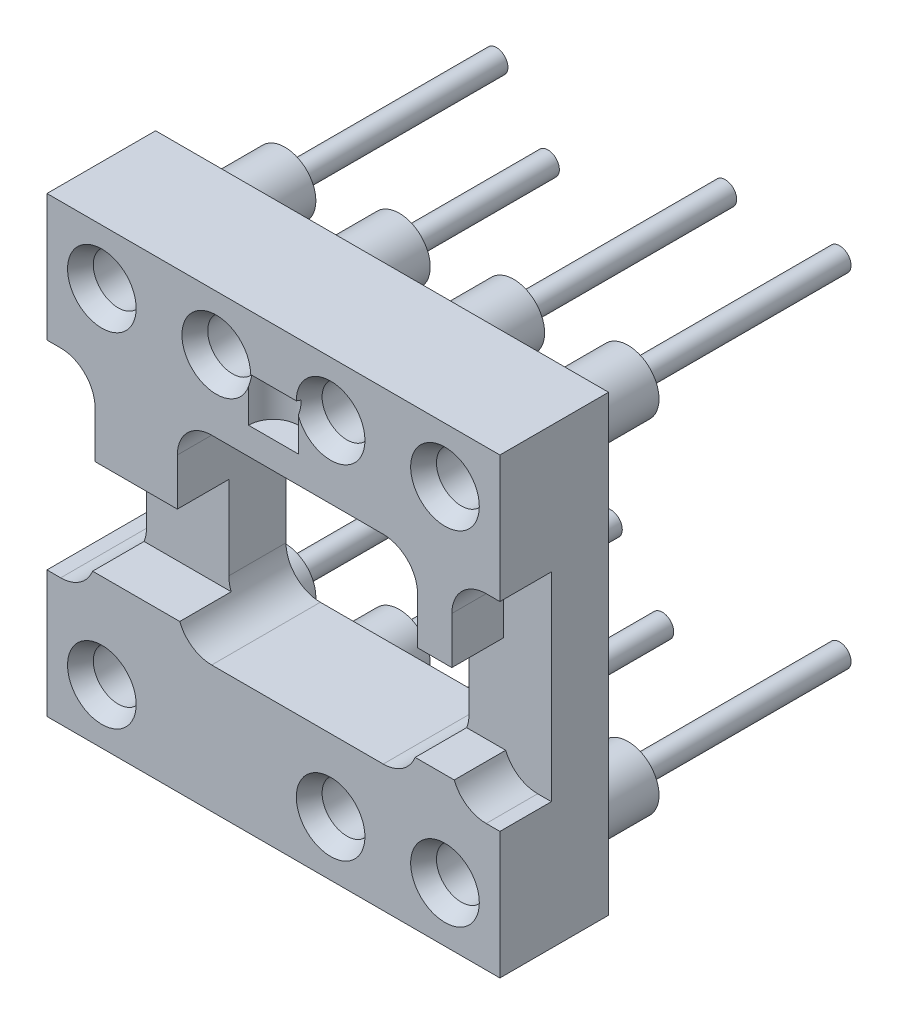
SolidWorks part; units mm, degrees
ref_plane "Plan de face" through (0, 0, 0) normal (0, 0, 1) x (1, 0, 0)
ref_plane "Plan de dessus" through (0, 0, 0) normal (0, 1, 0) x (1, 0, 0)
ref_plane "Plan de droite" through (0, 0, 0) normal (1, 0, 0) x (0, 0, -1)
sketch "Esquisse1" plane through (0, 0, 0) normal (0, 0, 1) x (1, 0, 0)
  line L0 (-5.0292, -5.0292) -> (5.0292, -5.0292)
  line L1 (5.0292, -5.0292) -> (5.0292, 5.0292)
  line L2 (5.0292, 5.0292) -> (-5.0292, 5.0292)
  line L3 (-5.0292, 5.0292) -> (-5.0292, -5.0292)
extrude "Boss.-Extru.1" add sketch "Esquisse1" against normal blind 2.413
sketch "Esquisse2" plane through (0, 0, -2.413) normal (0, 0, -1) x (-1, 0, 0)
  line L0 (2.1336, 2.2098) -> (-3.2004, 2.2098)
  line L1 (-3.2004, 2.2098) -> (-3.2004, -2.2098)
  line L2 (-3.2004, -2.2098) -> (2.1336, -2.2098)
  line L3 (2.1336, -2.2098) -> (2.1336, 2.2098)
extrude "Enlèv. mat.-Extru.1" cut sketch "Esquisse2" against normal through all
sketch "Esquisse3" plane through (3.2004, 0, 0) normal (-1, 0, 0) x (0, 0, 1)
  line L0 (0, -1.7272) -> (0, 0.4064)
  line L1 (0, 0.4064) -> (-1.143, 0.4064)
  line L2 (-1.143, 0.4064) -> (-1.143, -1.7272)
  line L3 (-1.143, -1.7272) -> (0, -1.7272)
extrude "Enlèv. mat.-Extru.2" cut sketch "Esquisse3" against normal through all
sketch "Esquisse4" plane through (0, 0, 0) normal (0, 0, 1) x (1, 0, 0)
  line L0 (5.0292, 2.2098) -> (3.9624, 2.2098)
  line L1 (3.9624, 2.2098) -> (3.9624, 0.4064)
  line L2 (3.9624, 0.4064) -> (5.0292, 0.4064)
  line L3 (5.0292, 0.4064) -> (5.0292, 2.2098)
extrude "Enlèv. mat.-Extru.3" cut sketch "Esquisse4" against normal blind 1.143
sketch "Esquisse5" plane through (0, 0, 0) normal (0, 0, 1) x (1, 0, 0)
  line L0 (5.0292, -1.7272) -> (4.0155, -1.7272)
  line L1 (4.7244, -2.2098) -> (5.0292, -2.2098)
  line L2 (5.0292, -2.2098) -> (5.0292, -1.7272)
  arc A0 (4.0155, -1.7272) -> (4.7244, -2.2098) centre (4.7244, -1.4478) ccw
extrude "Enlèv. mat.-Extru.4" cut sketch "Esquisse5" against normal blind 1.143
sketch "Esquisse6" plane through (0, 0, -2.413) normal (0, 0, -1) x (-1, 0, 0)
  line L0 (5.0292, -2.2098) -> (5.0292, 2.2098)
  line L1 (5.0292, 2.2098) -> (3.9624, 2.2098)
  line L2 (3.9624, 2.2098) -> (3.9624, -2.2098)
  line L3 (3.9624, -2.2098) -> (5.0292, -2.2098)
extrude "Enlèv. mat.-Extru.5" cut sketch "Esquisse6" against normal through all
sketch "Esquisse7" plane through (-2.1336, 0, 0) normal (1, 0, 0) x (0, 0, -1)
  line L0 (0, 0.4064) -> (0, -1.7272)
  line L1 (0, -1.7272) -> (1.143, -1.7272)
  line L2 (1.143, -1.7272) -> (1.143, 0.4064)
  line L3 (1.143, 0.4064) -> (0, 0.4064)
extrude "Enlèv. mat.-Extru.6" cut sketch "Esquisse7" against normal through all
ref_plane "Plan1" through (0, -3.81, 0) normal (0, 1, 0) x (-1, 0, 0)
sketch "Esquisse8" plane through (0, -3.81, 0) normal (0, 1, 0) x (-1, 0, 0)
  line L0 (-4.064, -8.763) -> (-3.81, -8.763)
  line L1 (-3.81, -8.763) -> (-3.81, -2.413)
  line L2 (-3.81, -2.413) -> (-4.4983, -2.413)
  line L3 (-4.4983, -2.413) -> (-4.4983, -4.064)
  line L4 (-4.4983, -4.064) -> (-4.064, -4.318)
  line L5 (-4.064, -4.318) -> (-4.064, -8.763)
  line L6 (-3.81, -8.763) -> (-3.81, -2.413) construction
revolve "Révolution1" add sketch "Esquisse8" angle 360 about L6 reverse direction yes
sketch "Esquisse9" plane through (0, -3.81, 0) normal (0, 1, 0) x (-1, 0, 0)
  line L0 (-1.524, -7.366) -> (-1.27, -7.366)
  line L1 (-1.27, -7.366) -> (-1.27, -2.413)
  line L2 (-1.27, -2.413) -> (-1.9583, -2.413)
  line L3 (-1.9583, -2.413) -> (-1.9583, -4.064)
  line L4 (-1.9583, -4.064) -> (-1.524, -4.318)
  line L5 (-1.524, -4.318) -> (-1.524, -7.366)
  line L6 (-1.27, -7.366) -> (-1.27, -2.413) construction
revolve "Révolution2" add sketch "Esquisse9" angle 360 about L6 reverse direction yes
sketch "Esquisse10" plane through (0, -3.81, 0) normal (0, 1, 0) x (-1, 0, 0)
  line L0 (1.016, -8.763) -> (1.27, -8.763)
  line L1 (1.27, -8.763) -> (1.27, -2.413)
  line L2 (1.27, -2.413) -> (0.5817, -2.413)
  line L3 (0.5817, -2.413) -> (0.5817, -4.064)
  line L4 (0.5817, -4.064) -> (1.016, -4.318)
  line L5 (1.016, -4.318) -> (1.016, -8.763)
  line L6 (1.27, -8.763) -> (1.27, -2.413) construction
revolve "Révolution3" add sketch "Esquisse10" angle 360 about L6 reverse direction yes
sketch "Esquisse11" plane through (0, -3.81, 0) normal (0, 1, 0) x (-1, 0, 0)
  line L0 (3.556, -8.763) -> (3.81, -8.763)
  line L1 (3.81, -8.763) -> (3.81, -2.413)
  line L2 (3.81, -2.413) -> (3.1217, -2.413)
  line L3 (3.1217, -2.413) -> (3.1217, -4.064)
  line L4 (3.1217, -4.064) -> (3.556, -4.318)
  line L5 (3.556, -4.318) -> (3.556, -8.763)
  line L6 (3.81, -8.763) -> (3.81, -2.413) construction
revolve "Révolution4" add sketch "Esquisse11" angle 360 about L6 reverse direction yes
ref_plane "Plan2" through (0, 3.81, 0) normal (0, 1, 0) x (-1, 0, 0)
sketch "Esquisse12" plane through (0, 3.81, 0) normal (0, 1, 0) x (-1, 0, 0)
  line L0 (-4.064, -8.763) -> (-3.81, -8.763)
  line L1 (-3.81, -8.763) -> (-3.81, -2.413)
  line L2 (-3.81, -2.413) -> (-4.4983, -2.413)
  line L3 (-4.4983, -2.413) -> (-4.4983, -4.064)
  line L4 (-4.4983, -4.064) -> (-4.064, -4.318)
  line L5 (-4.064, -4.318) -> (-4.064, -8.763)
  line L6 (-3.81, -8.763) -> (-3.81, -2.413) construction
revolve "Révolution5" add sketch "Esquisse12" angle 360 about L6 reverse direction yes
sketch "Esquisse13" plane through (0, 3.81, 0) normal (0, 1, 0) x (-1, 0, 0)
  line L0 (-1.524, -8.763) -> (-1.27, -8.763)
  line L1 (-1.27, -8.763) -> (-1.27, -2.413)
  line L2 (-1.27, -2.413) -> (-1.9583, -2.413)
  line L3 (-1.9583, -2.413) -> (-1.9583, -4.064)
  line L4 (-1.9583, -4.064) -> (-1.524, -4.318)
  line L5 (-1.524, -4.318) -> (-1.524, -8.763)
  line L6 (-1.27, -8.763) -> (-1.27, -2.413) construction
revolve "Révolution6" add sketch "Esquisse13" angle 360 about L6 reverse direction yes
sketch "Esquisse14" plane through (0, 3.81, 0) normal (0, 1, 0) x (-1, 0, 0)
  line L0 (1.016, -7.366) -> (1.27, -7.366)
  line L1 (1.27, -7.366) -> (1.27, -2.413)
  line L2 (1.27, -2.413) -> (0.5817, -2.413)
  line L3 (0.5817, -2.413) -> (0.5817, -4.064)
  line L4 (0.5817, -4.064) -> (1.016, -4.318)
  line L5 (1.016, -4.318) -> (1.016, -7.366)
  line L6 (1.27, -7.366) -> (1.27, -2.413) construction
revolve "Révolution7" add sketch "Esquisse14" angle 360 about L6 reverse direction yes
sketch "Esquisse15" plane through (0, 3.81, 0) normal (0, 1, 0) x (-1, 0, 0)
  line L0 (3.556, -8.763) -> (3.81, -8.763)
  line L1 (3.81, -8.763) -> (3.81, -2.413)
  line L2 (3.81, -2.413) -> (3.1217, -2.413)
  line L3 (3.1217, -2.413) -> (3.1217, -4.064)
  line L4 (3.1217, -4.064) -> (3.556, -4.318)
  line L5 (3.556, -4.318) -> (3.556, -8.763)
  line L6 (3.81, -8.763) -> (3.81, -2.413) construction
revolve "Révolution8" add sketch "Esquisse15" angle 360 about L6 reverse direction yes
hole_wizard "Perçage1" positions "Esquisse17" profile "Esquisse16" legacy
sketch "Esquisse17" plane through (0, 0, 0) normal (0, 0, 1) x (1, 0, 0)
  point P0 (3.81, -3.81)
sketch "Esquisse16" plane through (3.81, -3.81, 0) normal (1, 0, 0) x (0, -1, 0)
  line L0 (0, 0) -> (0, 1)
  line L1 (0, 1) -> (0.5525, 1)
  line L2 (0.5525, 1) -> (0.5525, 0)
  line L3 (0.5525, 0) -> (0, 0)
  line L4 (0, 110) -> (0, -10) construction
  dimension "Diamètre" = 1.1049
  dimension "Profondeur" = 1
hole_wizard "Perçage2" positions "Esquisse19" profile "Esquisse18" legacy
sketch "Esquisse19" plane through (0, 0, 0) normal (0, 0, 1) x (1, 0, 0)
  point P0 (-3.81, 3.81)
sketch "Esquisse18" plane through (-3.81, 3.81, 0) normal (1, 0, 0) x (0, -1, 0)
  line L0 (0, 0) -> (0, 1)
  line L1 (0, 1) -> (0.5525, 1)
  line L2 (0.5525, 1) -> (0.5525, 0)
  line L3 (0.5525, 0) -> (0, 0)
  line L4 (0, 110) -> (0, -10) construction
  dimension "Diamètre" = 1.1049
  dimension "Profondeur" = 1
hole_wizard "Perçage3" positions "Esquisse21" profile "Esquisse20" legacy
sketch "Esquisse21" plane through (0, 0, 0) normal (0, 0, 1) x (1, 0, 0)
  point P0 (1.27, -3.81)
sketch "Esquisse20" plane through (1.27, -3.81, 0) normal (1, 0, 0) x (0, -1, 0)
  line L0 (0, 0) -> (0, 1)
  line L1 (0, 1) -> (0.5525, 1)
  line L2 (0.5525, 1) -> (0.5525, 0)
  line L3 (0.5525, 0) -> (0, 0)
  line L4 (0, 110) -> (0, -10) construction
  dimension "Diamètre" = 1.1049
  dimension "Profondeur" = 1
hole_wizard "Perçage4" positions "Esquisse23" profile "Esquisse22" legacy
sketch "Esquisse23" plane through (0, 3.81, 0) normal (0, 1, 0) x (-1, 0, 0)
  point P0 (0, 0)
sketch "Esquisse22" plane through (0, 3.81, 0) normal (1, 0, 0) x (0, 0, 1)
  line L0 (0, 0) -> (0, 1)
  line L1 (0, 1) -> (0.5525, 1)
  line L2 (0.5525, 1) -> (0.5525, 0)
  line L3 (0.5525, 0) -> (0, 0)
  line L4 (0, 110) -> (0, -10) construction
  dimension "Diamètre" = 1.1049
  dimension "Profondeur" = 1
hole_wizard "Perçage5" positions "Esquisse25" profile "Esquisse24" legacy
sketch "Esquisse25" plane through (0, 0, 0) normal (0, 0, 1) x (1, 0, 0)
  point P0 (-3.81, -3.81)
sketch "Esquisse24" plane through (-3.81, -3.81, 0) normal (1, 0, 0) x (0, -1, 0)
  line L0 (0, 0) -> (0, 1)
  line L1 (0, 1) -> (0.5525, 1)
  line L2 (0.5525, 1) -> (0.5525, 0)
  line L3 (0.5525, 0) -> (0, 0)
  line L4 (0, 110) -> (0, -10) construction
  dimension "Diamètre" = 1.1049
  dimension "Profondeur" = 1
hole_wizard "Perçage6" positions "Esquisse27" profile "Esquisse26" legacy
sketch "Esquisse27" plane through (0, 0, 0) normal (0, 0, 1) x (1, 0, 0)
  point P0 (1.27, 3.81)
sketch "Esquisse26" plane through (1.27, 3.81, 0) normal (1, 0, 0) x (0, -1, 0)
  line L0 (0, 0) -> (0, 1)
  line L1 (0, 1) -> (0.5525, 1)
  line L2 (0.5525, 1) -> (0.5525, 0)
  line L3 (0.5525, 0) -> (0, 0)
  line L4 (0, 110) -> (0, -10) construction
  dimension "Diamètre" = 1.1049
  dimension "Profondeur" = 1
hole_wizard "Perçage7" positions "Esquisse29" profile "Esquisse28" legacy
sketch "Esquisse29" plane through (0, 0, 0) normal (0, 0, 1) x (1, 0, 0)
  point P0 (3.81, 3.81)
sketch "Esquisse28" plane through (3.81, 3.81, 0) normal (1, 0, 0) x (0, -1, 0)
  line L0 (0, 0) -> (0, 1)
  line L1 (0, 1) -> (0.5525, 1)
  line L2 (0.5525, 1) -> (0.5525, 0)
  line L3 (0.5525, 0) -> (0, 0)
  line L4 (0, 110) -> (0, -10) construction
  dimension "Diamètre" = 1.1049
  dimension "Profondeur" = 1
hole_wizard "Perçage8" positions "Esquisse31" profile "Esquisse30" legacy
sketch "Esquisse31" plane through (0, 0, 0) normal (0, 0, 1) x (1, 0, 0)
  point P0 (-1.27, 3.81)
sketch "Esquisse30" plane through (-1.27, 3.81, 0) normal (1, 0, 0) x (0, -1, 0)
  line L0 (0, 0) -> (0, 1)
  line L1 (0, 1) -> (0.5525, 1)
  line L2 (0.5525, 1) -> (0.5525, 0)
  line L3 (0.5525, 0) -> (0, 0)
  line L4 (0, 110) -> (0, -10) construction
  dimension "Diamètre" = 1.1049
  dimension "Profondeur" = 1
chamfer "Chanfrein1" distance 0.2095 angle 60 1 edges at (4.3625, -3.81, 0) first distance on face at (-3.2575, -3.81, 0)
chamfer "Chanfrein2" distance 0.2095 angle 60 1 edges at (-3.2575, 3.81, 0) first distance on face at (-0.7175, 3.81, 0)
chamfer "Chanfrein3" distance 0.2095 angle 60 1 edges at (1.8225, -3.81, 0) first distance on face at (4.572, -3.81, 0)
chamfer "Chanfrein4" distance 0.2095 angle 60 1 edges at (-3.2575, -3.81, 0) first distance on face at (2.032, -3.81, 0)
chamfer "Chanfrein5" distance 0.2095 angle 60 1 edges at (1.8225, 3.81, 0) first distance on face at (-3.048, 3.81, 0)
chamfer "Chanfrein6" distance 0.2095 angle 60 1 edges at (4.3625, 3.81, 0) first distance on face at (-3.048, 3.81, 0)
chamfer "Chanfrein7" distance 0.2095 angle 60 1 edges at (-0.7175, 3.81, 0) first distance on face at (4.572, 3.81, 0)
fillet "Congé1" radius 0.762 1 edges at (-2.1336, -2.2098, -1.2065) tangent propagation no
fillet "Congé2" radius 0.762 1 edges at (-3.9624, -2.2098, -1.2065) tangent propagation no
fillet "Congé3" radius 0.762 1 edges at (-2.1336, 2.2098, -1.2065) tangent propagation no
fillet "Congé4" radius 0.762 1 edges at (-3.9624, 2.2098, -1.2065) tangent propagation no
fillet "Congé5" radius 0.762 1 edges at (3.2004, -2.2098, -1.2065) tangent propagation no
fillet "Congé6" radius 0.762 1 edges at (3.9624, 2.2098, -0.5715) tangent propagation no
fillet "Congé7" radius 0.762 1 edges at (3.2004, 2.2098, -1.2065)
